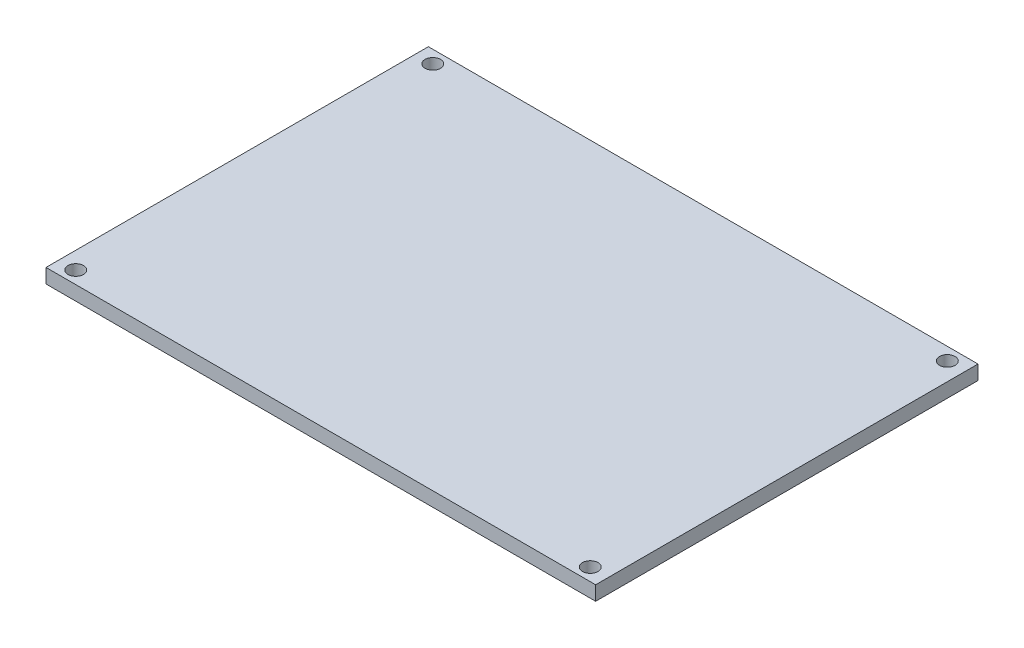
SolidWorks part; units mm, degrees
ref_plane "前视基准面" through (0, 0, 0) normal (0, 0, 1) x (1, 0, 0)
ref_plane "上视基准面" through (0, 0, 0) normal (0, 1, 0) x (1, 0, 0)
ref_plane "右视基准面" through (0, 0, 0) normal (1, 0, 0) x (0, 0, -1)
other "Configuration Table"
sketch "草图1" plane through (0, 0, 0) normal (0, 1, 0) x (1, 0, 0)
  line L0 (-53.925, 37.35) -> (-53.925, -37.35) construction
  line L1 (-57.5, 40) -> (57.5, 40)
  line L2 (-57.5, 40) -> (-57.5, -40)
  line L3 (-57.5, -40) -> (57.5, -40)
  line L4 (57.5, 40) -> (57.5, -40)
  line L5 (-57.5, 40) -> (57.5, -40) construction
  line L6 (-57.5, -40) -> (57.5, 40) construction
  line L7 (-53.925, -37.35) -> (53.725, -37.35) construction
  line L8 (53.725, -37.35) -> (53.725, 37.35) construction
  line L9 (53.725, 37.35) -> (-53.925, 37.35) construction
  circle A0 centre (-53.925, 37.35) radius 1.625
  circle A1 centre (53.725, 37.35) radius 1.625
  circle A2 centre (-53.925, -37.35) radius 1.625
  circle A3 centre (53.725, -37.35) radius 1.625
  point P0 (0, 0)
  dimension "D3" = 3.25
  dimension "D4" = 3.25
  dimension "D5" = 3.25
  dimension "D6" = 3.25
  dimension "D1" = 115
  dimension "D2" = 80
  dimension "D7" = 107.65
  dimension "D8" = 74.7
  dimension "D9" = 37.35
  dimension "D10" = 53.925
extrude "凸台-拉伸1" add sketch "草图1" along normal blind 3 contours L1 L4 L3 L2
extrude "切除-拉伸3" cut sketch "草图1<4>" along normal blind 3 flip side to cut
sketch "草图1<4>" plane through (0, 0, 0) normal (0, 1, 0) x (1, 0, 0) same geometry as "草图1"
